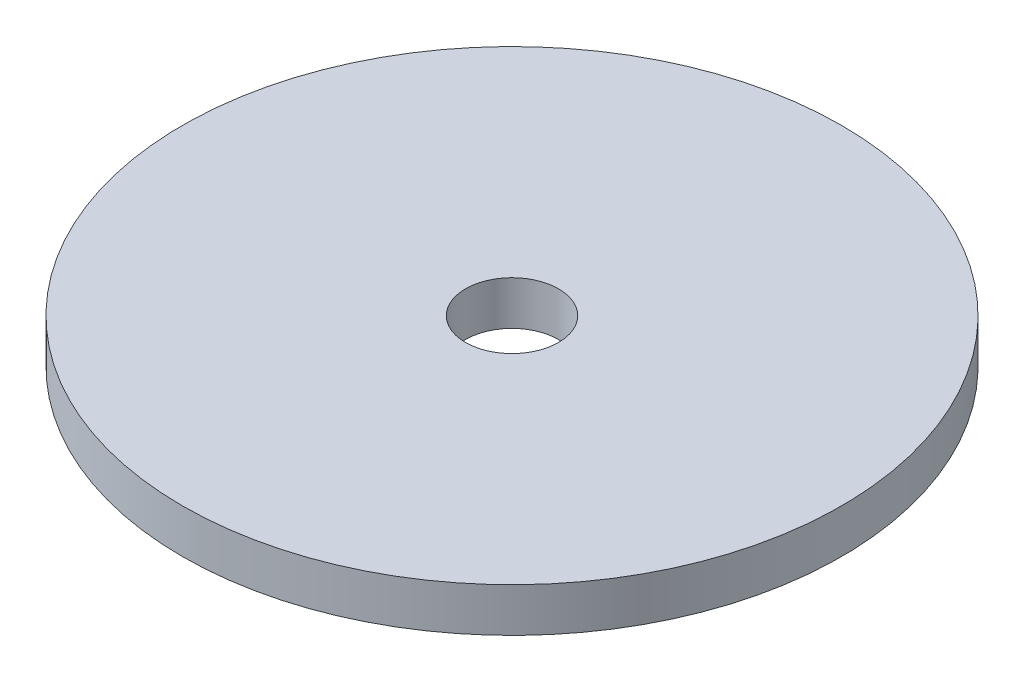
SolidWorks part; units mm, degrees
ref_plane "Front Plane" through (0, 0, 0) normal (0, 0, 1) x (1, 0, 0)
ref_plane "Top Plane" through (0, 0, 0) normal (0, 1, 0) x (1, 0, 0)
ref_plane "Right Plane" through (0, 0, 0) normal (1, 0, 0) x (0, 0, -1)
sketch "Sketch1" plane through (0, 0, 0) normal (0, 1, 0) x (1, 0, 0)
  circle A0 centre (0, 0) radius 22.5
  circle A9 centre (0, 0) radius 3.175
  dimension "D1" = 45
  dimension "D2" = 6.35
extrude "Boss-Extrude1" add sketch "Sketch1" against normal blind 3 contours A0 region at (-21.8636, 0, 0)
